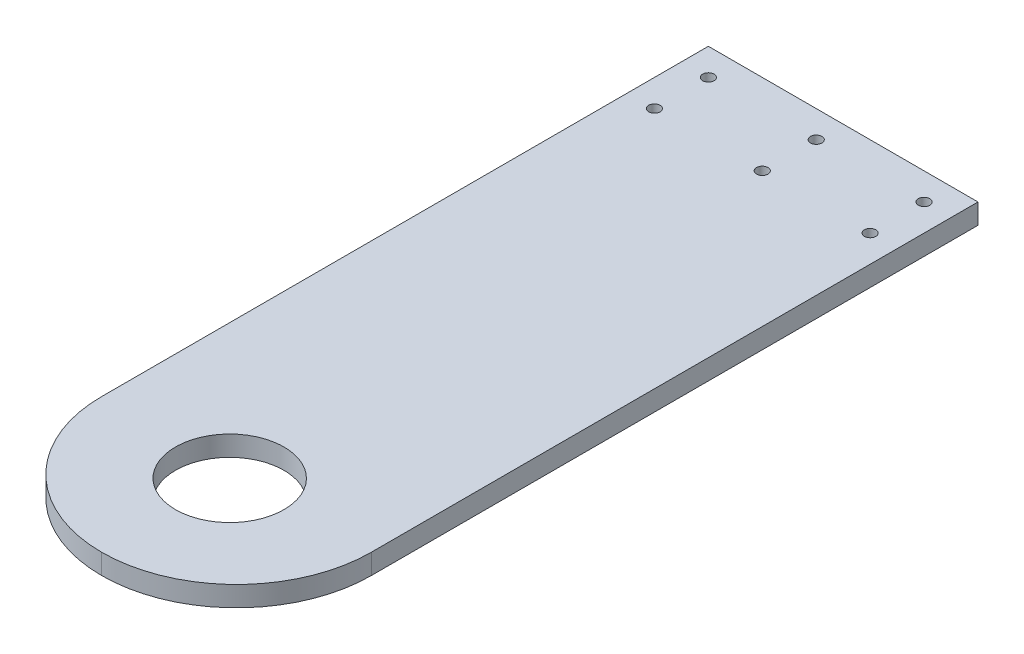
SolidWorks part; units mm, degrees
material "6061-T6 (SS)"
ref_plane "Front Plane" through (0, 0, 0) normal (0, 0, 1) x (1, 0, 0)
ref_plane "Top Plane" through (0, 0, 0) normal (0, 1, 0) x (1, 0, 0)
ref_plane "Right Plane" through (0, 0, 0) normal (1, 0, 0) x (0, 0, -1)
sketch "Sketch1" plane through (0, 0, 0) normal (0, 1, 0) x (1, 0, 0)
  line L1 (0, 0) -> (80, 0)
  line L2 (0, 0) -> (0, -230)
  line L3 (0, -230) -> (80, -230)
  line L4 (80, 0) -> (80, -230)
  dimension "D1" = 80
  dimension "D2" = 230
extrude "Boss-Extrude1" add sketch "Sketch1" along normal blind 6
sketch "Sketch5" plane through (0, 6, 0) normal (0, 1, 0) x (1, 0, 0)
  circle A1 centre (40, -192) radius 20
  circle A2 centre (40, -192) radius 48.5 construction
  point P1 (40, -192)
hole_wizard "Ø32.0 (32) Diameter Hole1" positions "Sketch5" profile "Sketch6" hole size "Ø32.0" standard "DIN" end condition through all
sketch "Sketch6" plane through (40, 6, 192) normal (1, 0, 0) x (0, 0, 1)
  line L0 (0, 0) -> (0, 6)
  line L1 (0, 6) -> (16.1, 6)
  line L2 (16.1, 6) -> (16.1, 0)
  line L5 (16.1, 0) -> (0, 0)
  line L11 (0, -6.35) -> (0, 107.95) construction
  dimension "Thru Hole Dia." = 32.2
  dimension "Thru Hole Depth" = 6
fillet "Fillet1" radius 40 2 edges at (0, 3, 230) (80, 3, 230)
sketch "Sketch9" plane through (0, 0, 0) normal (0, 1, 0) x (1, 0, 0)
  line L0 (40, 0) -> (40, -57.4233) construction
  line L1 (80, 0) -> (0, 0) construction
  point P0 (8, -18)
  point P6 (40, -18)
  point P7 (72, -18)
  point P8 (40, -34)
  point P9 (72, -34)
  point P10 (8, -34)
  dimension "D3" = 18
  dimension "D1" = 3
  dimension "D2" = 2
hole_wizard "CBORE for M3 Hex Socket Head Cap Screw1" positions "Sketch9" profile "Sketch8" counterbore size "M3" standard "DIN" end condition through all
sketch "Sketch8" plane through (8, 0, 18) normal (1, 0, 0) x (0, 0, -1)
  line L0 (0, 0) -> (0, 6)
  line L1 (0, 6) -> (1.7, 6)
  line L3 (1.7, 6) -> (1.7, 3.4)
  line L4 (1.7, 3.4) -> (3.25, 3.4)
  line L5 (3.25, 3.4) -> (3.25, 0)
  line L7 (3.25, 0) -> (0, 0)
  line L11 (0, -6.35) -> (0, 107.95) construction
  dimension "Thru Hole Dia." = 3.4
  dimension "Thru Hole Depth" = 6
  dimension "C'Bore Dia." = 6.5
  dimension "C'Bore Depth" = 3.4
sketch "Sketch10" plane through (0, 6, 0) normal (0, 1, 0) x (1, 0, 0)
  line L0 (80, -190) -> (80, 0) construction
  line L1 (0, 0) -> (80, 0)
  line L2 (0, 0) -> (0, -10)
  line L3 (0, -10) -> (80, -10)
  line L4 (80, 0) -> (80, -10)
  dimension "D1" = 10
extrude "Cut-Extrude1" cut sketch "Sketch10" against normal through all
